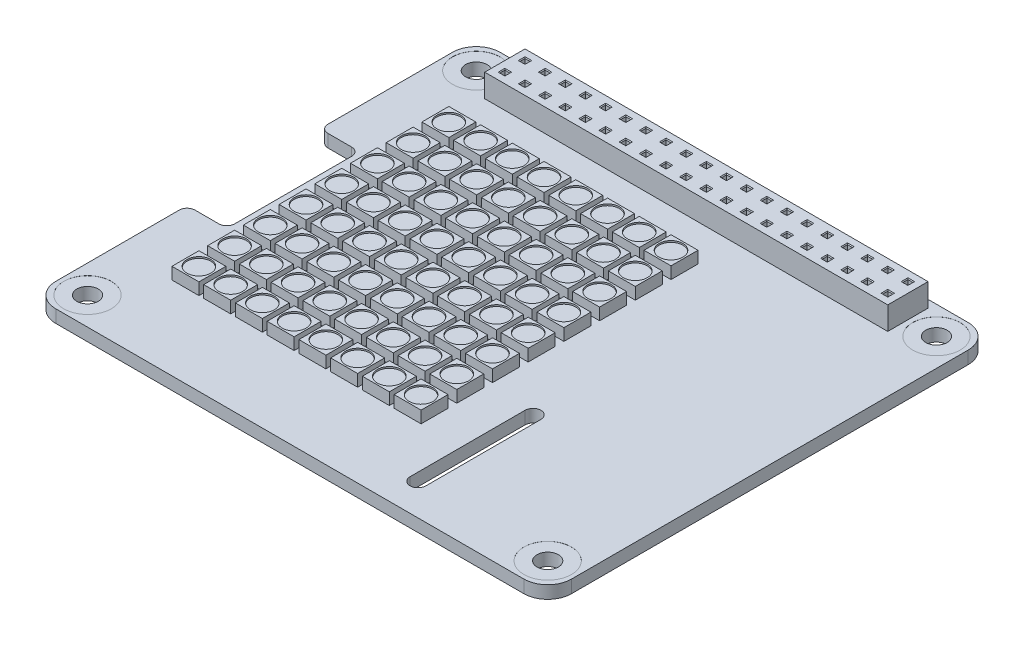
SolidWorks part; units mm, degrees
other "Camera1"
material "Silicon"
ref_plane "Front Plane" through (0, 0, 0) normal (0, 0, 1) x (1, 0, 0)
ref_plane "Top Plane" through (0, 0, 0) normal (0, 1, 0) x (1, 0, 0)
ref_plane "Right Plane" through (0, 0, 0) normal (1, 0, 0) x (0, 0, -1)
sketch "BaseS" plane through (0, 0, 0) normal (0, 1, 0) x (1, 0, 0)
  line L1 (-42.5, 28) -> (42.5, 28)
  line L2 (-42.5, 28) -> (-42.5, -28)
  line L3 (-42.5, -28) -> (42.5, -28)
  line L4 (42.5, 28) -> (42.5, -28)
  line L5 (-42.5, 28) -> (42.5, -28) construction
  line L6 (-42.5, -28) -> (42.5, 28) construction
  point P0 (0, 0)
  dimension "Width" = 56
  dimension "Length" = 85
extrude "Base" add sketch "BaseS" along normal mid plane 1.6
hole_wizard "M2.5 Clearance Hole" positions "Sketch2" profile "Sketch3" hole size "M2.5" standard "ANSI Metric" end condition through all
sketch "Sketch2" plane through (0, 0.8, 0) normal (0, 1, 0) x (1, 0, 0)
  line L0 (-39, 24.5) -> (-39, -24.5) construction
  line L2 (-42.5, 28) -> (-42.5, -28) construction
  line L3 (42.5, 28) -> (-42.5, 28) construction
  line L4 (-42.5, -28) -> (42.5, -28) construction
  point P0 (-39, 24.5)
  point P2 (-39, -24.5)
  dimension "XDim" = 3.5
  dimension "YDim" = 3.5
  dimension "D3" = 3.5
sketch "Sketch3" plane through (-39, 0.8, -24.5) normal (1, 0, 0) x (0, 0, 1)
  line L0 (0, 0) -> (0, 1.6)
  line L1 (0, 1.6) -> (1.35, 1.6)
  line L2 (1.35, 1.6) -> (1.35, 0)
  line L5 (1.35, 0) -> (0, 0)
  line L11 (0, -6.35) -> (0, 107.95) construction
  dimension "Thru Hole Dia." = 2.7
  dimension "Thru Hole Depth" = 1.6
sketch "FastenerAreaS" plane through (0, 0.8, 0) normal (0, 1, 0) x (1, 0, 0)
  circle A0 centre (-39, -24.5) radius 3
  circle A1 centre (-39, -24.5) radius 1.35 construction
  circle A2 centre (-39, -24.5) radius 1.35
  circle A3 centre (-39, 24.5) radius 1.35 construction
  circle A4 centre (-39, 24.5) radius 1.35
  circle A5 centre (-39, 24.5) radius 3
  dimension "RefDia" = 6
  dimension "DiaControl" = 1.65
extrude "FastenerArea" cut sketch "FastenerAreaS" against normal blind 0.01
pattern_linear "HLP FastenerHoles" count 2 spacing 58 along (1, 0, 0) of "M2.5 Clearance Hole", "FastenerArea"
mirror "VM FA" about plane through (0, 0, 0) normal (0, 1, 0) of "HLP FastenerHoles", "FastenerArea"
hole_wizard "Ø1.0 (1) Diameter Hole IO" positions "Sketch7" profile "Sketch8" hole size "Ø1.0" standard "ANSI Metric" end condition through all
sketch "Sketch7" plane through (0, 0.8, 0) normal (0, 1, 0) x (1, 0, 0)
  circle A0 centre (-39, 24.5) radius 1.35 construction
  point P0 (-34.13, 25.77)
  dimension "YDim" = 1.27
  dimension "XDim" = 4.87
sketch "Sketch8" plane through (-34.13, 0.8, -25.77) normal (1, 0, 0) x (0, 0, 1)
  line L0 (0, 0) -> (0, 1.6)
  line L1 (0, 1.6) -> (0.5, 1.6)
  line L2 (0.5, 1.6) -> (0.5, 0)
  line L5 (0.5, 0) -> (0, 0)
  line L11 (0, -6.35) -> (0, 107.95) construction
  dimension "Thru Hole Dia." = 1
  dimension "Thru Hole Depth" = 1.6
pattern_linear "LP DiaHole IO" count 20 spacing 2.54 along (1, 0, 0) count 2 spacing 2.54 along (0, 0, 1) of "Ø1.0 (1) Diameter Hole IO"
fillet "CornerRadius" radius 3 4 edges at (42.5, 0, -28) (42.5, 0, 28) (-42.5, 0, -28) (-42.5, 0, 28)
sketch "Sketch9" plane through (0, 0.8, 0) normal (0, 1, 0) x (1, 0, 0)
  line L0 (22.5, 28) -> (22.5, -28)
  line L1 (39.5, 28) -> (-39.5, 28) construction
  line L2 (-39.5, -28) -> (39.5, -28) construction
  line L3 (-42.5, 25) -> (-42.5, -25) construction
  line L4 (42.5, -25) -> (42.5, 25) construction
  line L5 (22.5, -28) -> (39.5, -28)
  line L6 (42.5, -25) -> (42.5, 25)
  line L7 (39.5, 28) -> (22.5, 28)
  arc A0 (39.5, -28) -> (42.5, -25) centre (39.5, -25) ccw construction
  arc A1 (42.5, 25) -> (39.5, 28) centre (39.5, 25) ccw construction
  arc A2 (39.5, -28) -> (42.5, -25) centre (39.5, -25) ccw
  arc A3 (42.5, 25) -> (39.5, 28) centre (39.5, 25) ccw
  dimension "D1" = 65
extrude "Cut-Extrude1" cut sketch "Sketch9" against normal through all
fillet "Fillet1" radius 3 2 edges at (22.5, 0, 28) (22.5, 0, -28)
sketch "Sketch10" plane through (0, 0.8, 0) normal (0, 1, 0) x (1, 0, 0)
  line L0 (-42.5, 8.3) -> (-37.5, 8.3)
  line L1 (-42.5, 25) -> (-42.5, -25) construction
  line L2 (-37.5, 8.3) -> (-37.5, -8.45)
  line L3 (-37.5, -8.45) -> (-42.5, -8.45)
  line L4 (-42.5, -8.45) -> (-42.5, 8.3)
  dimension "D1" = 5
  dimension "D2" = 16.75
  dimension "D3" = 8.3
extrude "Cut-Extrude2" cut sketch "Sketch10" against normal through all
fillet "Fillet2" radius 1 4 edges at (-42.5, 0, 8.45) (-37.5, 0, 8.45) (-37.5, 0, -8.3) (-42.5, 0, -8.3)
sketch "Sketch11" plane through (0, 0.8, 0) normal (0, 1, 0) x (1, 0, 0)
  line L0 (2.15, -9.5) -> (2.15, -24) construction
  line L1 (3.15, -9.5) -> (3.15, -24)
  line L2 (1.15, -9.5) -> (1.15, -24)
  line L3 (22.5, 25) -> (22.5, -25) construction
  line L4 (-39.5, -28) -> (19.5, -28) construction
  arc A0 (3.15, -9.5) -> (1.15, -9.5) centre (2.15, -9.5) ccw
  arc A1 (1.15, -24) -> (3.15, -24) centre (2.15, -24) ccw
  point P2 (2.15, -16.75)
  dimension "D1" = 20.35
  dimension "D2" = 1
  dimension "D3" = 14.5
  dimension "D4" = 11.25
extrude "Cut-Extrude3" cut sketch "Sketch11" against normal through all
sketch "Sketch12" plane through (0, -0.8, 0) normal (0, -1, 0) x (1, 0, 0)
  line L0 (-35.4, -27.04) -> (-35.4, -21.96)
  line L1 (-35.4, -21.96) -> (15.4, -21.96)
  line L2 (15.4, -21.96) -> (15.4, -27.04)
  line L3 (15.4, -27.04) -> (-35.4, -27.04)
  circle A0 centre (-39, -24.5) radius 1.35 construction
  dimension "D1" = 5.08
  dimension "D2" = 50.8
  dimension "D3" = 3.6
  dimension "D4" = 2.54
extrude "Boss-Extrude1" add sketch "Sketch12" along normal blind 5.8
sketch "Sketch14" plane through (0, -6.6, 0) normal (0, -1, 0) x (1, 0, 0)
  line L0 (-35.4, -27.04) -> (15.4, -27.04) construction
  line L1 (14.45, -25.45) -> (13.81, -25.45)
  line L2 (14.45, -25.45) -> (14.45, -26.09)
  line L3 (14.45, -26.09) -> (13.81, -26.09)
  line L4 (13.81, -25.45) -> (13.81, -26.09)
  line L5 (14.45, -25.45) -> (13.81, -26.09) construction
  line L6 (14.45, -26.09) -> (13.81, -25.45) construction
  line L7 (15.4, -27.04) -> (15.4, -21.96) construction
  point P0 (14.13, -25.77)
  dimension "D1" = 0.64
  dimension "D2" = 0.64
  dimension "D3" = 0.95
  dimension "D4" = 0.95
extrude "Cut-Extrude4" cut sketch "Sketch14" against normal blind 5.8
chamfer "Chamfer1" distance 0.3 angle 45 4 edges at (14.13, -6.6, -25.45) (14.45, -6.6, -25.77) (13.81, -6.6, -25.77) (14.13, -6.6, -26.09)
pattern_linear "LPattern1" count 20 spacing 2.54 along (-1, 0, 0) count 2 spacing 2.54 along (0, 0, 1) of "Chamfer1", "Cut-Extrude4"
sketch "Sketch15" plane through (0, 0.8, 0) normal (0, 1, 0) x (1, 0, 0)
  line L0 (15.4, 21.96) -> (15.4, 27.04)
  line L1 (15.4, 27.04) -> (-35.4, 27.04)
  line L2 (-35.4, 27.04) -> (-35.4, 21.96)
  line L3 (-35.4, 21.96) -> (15.4, 21.96)
  circle A0 centre (-39, 24.5) radius 1.35 construction
  dimension "D1" = 5.08
  dimension "D2" = 50.8
  dimension "D3" = 3.6
  dimension "D4" = 2.54
extrude "Boss-Extrude2" add sketch "Sketch15" along normal blind 2.9
sketch "Sketch16" plane through (0, 3.7, 0) normal (0, 1, 0) x (1, 0, 0)
  line L0 (15.4, 27.04) -> (-35.4, 27.04) construction
  line L1 (-33.81, 26.09) -> (-34.45, 26.09)
  line L2 (-33.81, 26.09) -> (-33.81, 25.45)
  line L3 (-33.81, 25.45) -> (-34.45, 25.45)
  line L4 (-34.45, 26.09) -> (-34.45, 25.45)
  line L5 (-33.81, 26.09) -> (-34.45, 25.45) construction
  line L6 (-33.81, 25.45) -> (-34.45, 26.09) construction
  line L7 (-35.4, 27.04) -> (-35.4, 21.96) construction
  point P0 (-34.13, 25.77)
  dimension "D1" = 0.64
  dimension "D2" = 0.64
  dimension "D3" = 0.95
  dimension "D4" = 0.95
extrude "Cut-Extrude5" cut sketch "Sketch16" against normal blind 2.9
chamfer "Chamfer2" distance 0.1 angle 45 4 edges at (-33.81, 3.7, -25.77) (-34.13, 3.7, -26.09) (-34.45, 3.7, -25.77) (-34.13, 3.7, -25.45)
pattern_linear "LPattern2" count 20 spacing 2.54 along (1, 0, 0) count 2 spacing 2.54 along (0, 0, 1) of "Chamfer2", "Cut-Extrude5"
sketch "Sketch17" plane through (0, 0.8, 0) normal (0, 1, 0) x (1, 0, 0)
  line L0 (-35.32, 17.36) -> (-35.32, 13.96)
  line L5 (-35.32, 13.96) -> (-31.92, 13.96)
  line L6 (-31.92, 13.96) -> (-31.92, 17.36)
  line L7 (-31.92, 17.36) -> (-35.32, 17.36)
  line L8 (-35.4, 21.96) -> (15.4, 21.96) construction
  line L9 (-42.5, 25) -> (-42.5, 9.3) construction
  dimension "D1" = 3.4
  dimension "D2" = 3.4
  dimension "D3" = 4.6
  dimension "D4" = 7.18
extrude "Boss-Extrude3" add sketch "Sketch17" along normal blind 1.5
sketch "Sketch18" plane through (0, 2.3, 0) normal (0, 1, 0) x (1, 0, 0)
  line L0 (-35.32, 17.36) -> (-31.92, 13.96) construction
  line L1 (-31.92, 17.36) -> (-35.32, 13.96) construction
  line L2 (-35.32, 13.96) -> (-31.92, 13.96) construction
  line L3 (-35.32, 17.36) -> (-35.32, 13.96) construction
  circle A1 centre (-33.62, 15.66) radius 1.5
  dimension "D1" = 3
extrude "Cut-Extrude6" cut sketch "Sketch18" against normal blind 0.2
pattern_linear "LPattern3" count 8 spacing 4.5 along (0, 0, 1) count 8 spacing 4 along (1, 0, 0) of "Boss-Extrude3", "Cut-Extrude6"
